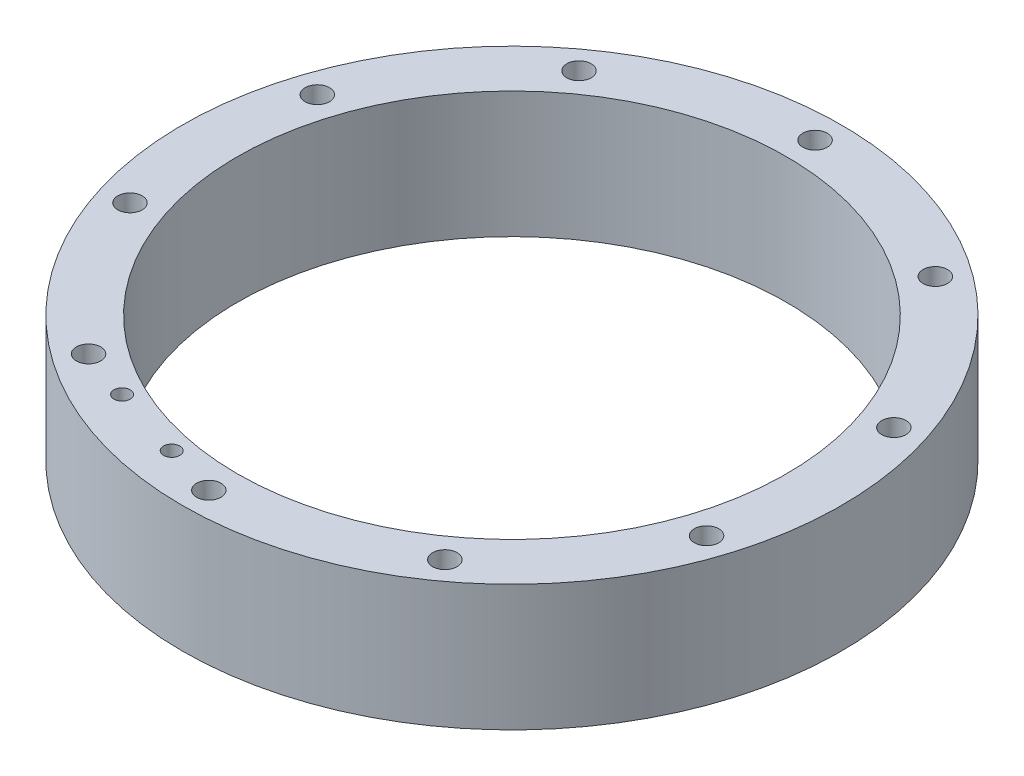
SolidWorks part; units mm, degrees
ref_plane "Front Plane" through (0, 0, 0) normal (0, 0, 1) x (1, 0, 0)
ref_plane "Top Plane" through (0, 0, 0) normal (0, 1, 0) x (1, 0, 0)
ref_plane "Right Plane" through (0, 0, 0) normal (1, 0, 0) x (0, 0, -1)
sketch "Sketch1" plane through (0, 0, 0) normal (0, 1, 0) x (1, 0, 0)
  circle A0 centre (0, 0) radius 40.5
  circle A1 centre (0, 0) radius 37.25 construction
  circle A2 centre (0, 37.25) radius 1.5
  circle A3 centre (21.895, 30.1359) radius 1.5
  circle A4 centre (35.4269, 11.5109) radius 1.5
  circle A5 centre (35.4269, -11.5109) radius 1.5
  circle A6 centre (21.895, -30.1359) radius 1.5
  circle A7 centre (0, -37.25) radius 1.5
  circle A8 centre (-21.895, -30.1359) radius 1.5
  circle A9 centre (-35.4269, -11.5109) radius 1.5
  circle A10 centre (-35.4269, 11.5109) radius 1.5
  circle A11 centre (-21.895, 30.1359) radius 1.5
  circle A12 centre (0, 0) radius 33.75
  point P26 (0, 0)
  dimension "D1" = 81
  dimension "D2" = 74.5
  dimension "D3" = 3
  dimension "D5" = 67.5
  dimension "D4" = 10
extrude "Boss-Extrude1" add sketch "Sketch1" along normal blind 15.5
sketch "Sketch2" plane through (0, 15.5, 0) normal (0, 1, 0) x (1, 0, 0)
  line L0 (-21.895, -30.1359) -> (0, -37.25) construction
  line L1 (-6.4835, -35.3254) -> (-15.5185, -32.3898) construction
  line L2 (-11.001, -33.8576) -> (-10.9475, -33.6929) construction
  circle A0 centre (-6.4835, -35.3254) radius 1
  circle A1 centre (-15.5185, -32.3898) radius 1
  point P10 (-5.6992, -35.2161)
  dimension "D1" = 2
  dimension "D2" = 0.1731
  dimension "D3" = 9.5
extrude "Cut-Extrude1" cut sketch "Sketch2" against normal through all
